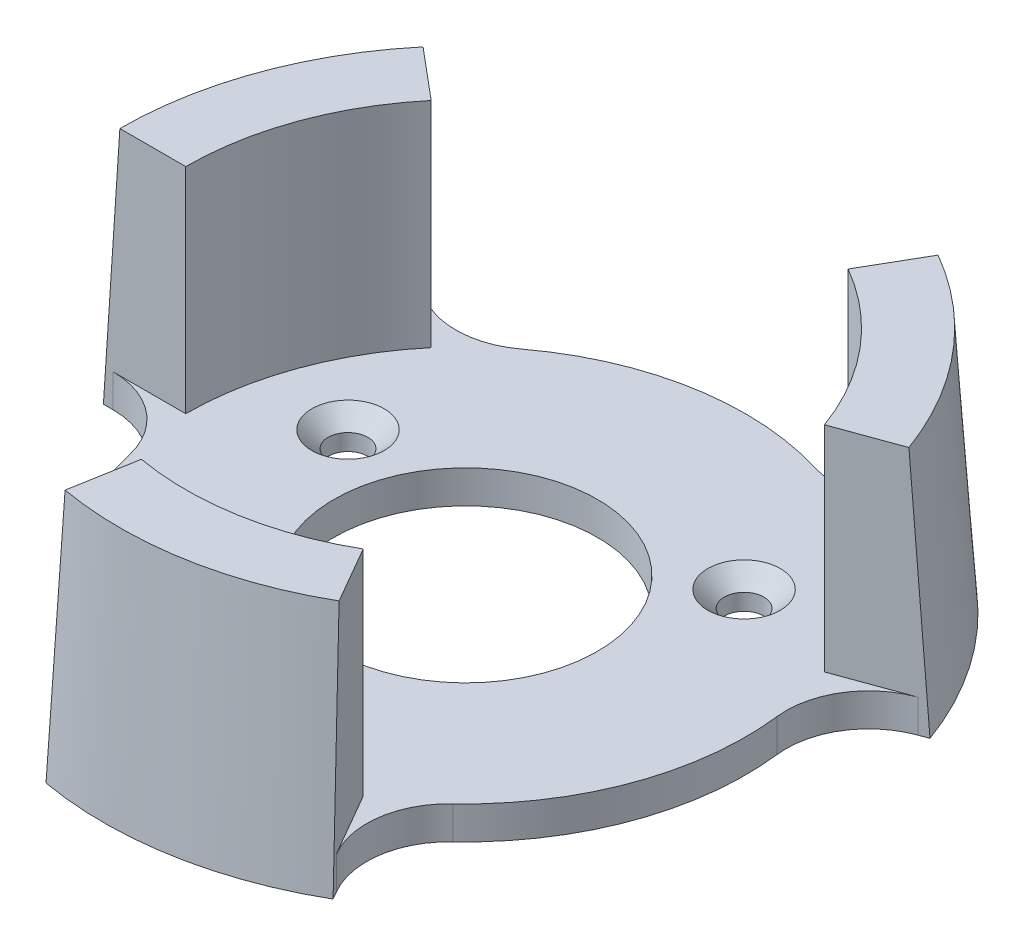
SolidWorks part; units mm, degrees
ref_plane "Front Plane" through (0, 0, 0) normal (0, 0, 1) x (1, 0, 0)
ref_plane "Top Plane" through (0, 0, 0) normal (0, 1, 0) x (1, 0, 0)
ref_plane "Right Plane" through (0, 0, 0) normal (1, 0, 0) x (0, 0, -1)
sketch "Sketch1" plane through (0, 0, 0) normal (0, 1, 0) x (1, 0, 0)
  circle A0 centre (0, 0) radius 8
  circle A1 centre (0, 0) radius 17
  dimension "D1" = 16
  dimension "D2" = 34
extrude "Boss-Extrude4" add sketch "Sketch1" along normal blind 2 contours A1 | A0
sketch "Sketch5" plane through (0, 0, 0) normal (0, 0, 1) x (1, 0, 0)
  line L0 (-17, 0) -> (-22, 0)
  line L1 (-17, 0) -> (-17, 15)
  line L2 (-17, 15) -> (-21, 15)
  line L3 (-21, 15) -> (-22, 0)
  line L4 (-17, 0) -> (17, 0) construction
  line L5 (0, 9.8137) -> (0, -8.5535) construction
  dimension "D1" = 15
  dimension "D2" = 5
  dimension "D3" = 4
revolve "Revolve2" add sketch "Sketch5" angle 40 about L5 other way angle 40
pattern_circular "CirPattern1" count 3 over 360 about axis through (0, 2, 0) along (0, 1, 0) of "Revolve2"
fillet "Fillet1" radius 5 6 edges at (8.5, 1, 14.7224) (15.9748, 1, -5.8143) (8.5, 1, -14.7224) (-13.0228, 1, -10.9274) (-17, 1, 0) (-2.952, 1, 16.7417)
sketch "Sketch6" plane through (0, 2, 0) normal (0, 1, 0) x (1, 0, 0)
  line L0 (-15.9748, 5.8143) -> (20.5236, -7.47) construction
  line L1 (13.0228, 10.9274) -> (-17.0854, -14.3363) construction
  line L2 (2.952, -16.7417) -> (-4.6806, 26.545) construction
  arc A0 (-13.0228, 10.9274) -> (-17, 0) centre (0, 0) ccw construction
  arc A1 (15.9748, 5.8143) -> (8.5, 14.7224) centre (0, 0) ccw construction
  arc A2 (-2.952, -16.7417) -> (8.5, -14.7224) centre (0, 0) ccw construction
  circle A3 centre (0, 0) radius 12 construction
  point P19 (-11.2361, 4.0896)
  point P20 (2.0838, -11.8177)
  point P22 (0.0402, -0.0146)
  point P23 (9.1925, 7.7135)
  dimension "D1" = 24
hole_wizard "CSK for M2 Countersunk Flat Head Screw1" positions "Sketch12" profile "Sketch13" countersink size "M2" standard "ISO" end condition through all
sketch "Sketch12" plane through (0, 2, 0) normal (0, 1, 0) x (1, 0, 0)
  point P0 (2.0838, -11.8177)
  point P3 (9.1925, 7.7135)
  point P6 (-11.2361, 4.0896)
sketch "Sketch13" plane through (2.0838, 2, 11.8177) normal (1, 0, 0) x (0, 0, 1)
  line L0 (0, 0) -> (0, 2)
  line L1 (0, 2) -> (1.2, 2)
  line L2 (1.2, 2) -> (1.2, 1)
  line L3 (1.2, 1) -> (2.2, 0)
  line L5 (2.2, 0) -> (0, 0)
  line L6 (-1.2, 1) -> (-2.2, 0) construction
  line L11 (0, -6.35) -> (0, 107.95) construction
  dimension "Thru Hole Dia." = 2.4
  dimension "Thru Hole Depth" = 2
  dimension "Near C'Sink Dia." = 4.4
  dimension "Near C'Sink Angle" = 90
sketch "Sketch18" plane through (0, 0, 0) normal (0, -1, 0) x (1, 0, 0)
  line L0 (13.0228, -10.9274) -> (-17.0854, 14.3363) construction
